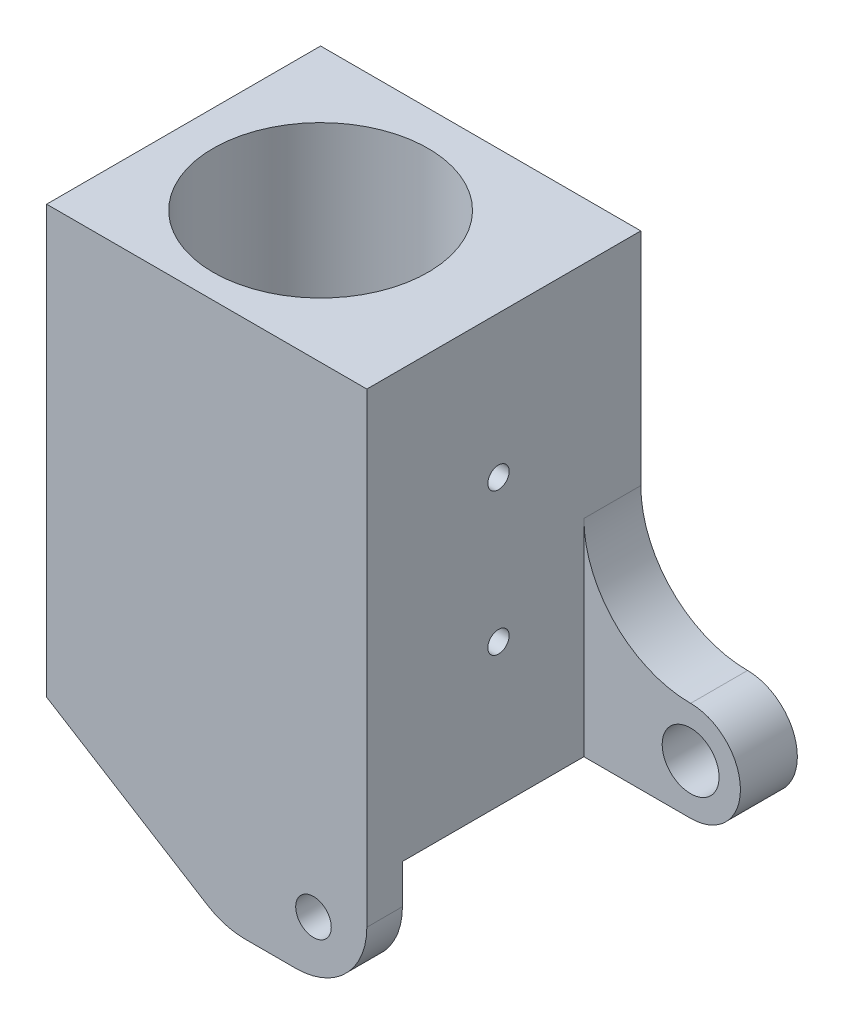
SolidWorks part; units mm, degrees
ref_plane "前基準面" through (0, 0, 0) normal (0, 0, 1) x (1, 0, 0)
ref_plane "上基準面" through (0, 0, 0) normal (0, 1, 0) x (1, 0, 0)
ref_plane "右基準面" through (0, 0, 0) normal (1, 0, 0) x (0, 0, -1)
sketch "草圖1" plane through (0, 0, 0) normal (0, 1, 0) x (1, 0, 0)
  line L1 (-20, 20) -> (25, 20)
  line L2 (-20, 20) -> (-20, -18.5)
  line L3 (-20, -18.5) -> (25, -18.5)
  line L4 (25, 20) -> (25, -18.5)
  dimension "D1" = 20
  dimension "D2" = 38.5
  dimension "D3" = 45
  dimension "D4" = 20
extrude "填料-伸長1" add sketch "草圖1" along normal blind 60
sketch "草圖2" plane through (0, 60, 0) normal (0, 1, 0) x (1, 0, 0)
  circle A0 centre (0, 0) radius 15.1
  dimension "D1" = 30.2
extrude "除料-伸長1" cut sketch "草圖2" against normal blind 50
sketch "草圖3" plane through (0, 0, 18.5) normal (0, 0, 1) x (1, 0, 0)
  line L1 (-20, 0) -> (5, -15.5)
  line L2 (5, -15.5) -> (25, -15.5)
  line L3 (25, -15.5) -> (25, 0)
  line L4 (25, 0) -> (-20, 0)
  circle A1 centre (17.5, -8) radius 2.5
  dimension "D1" = 5
  dimension "D2" = 20
  dimension "D3" = 15.5
  dimension "D4" = 7.5
  dimension "D5" = 8
extrude "填料-伸長2" add sketch "草圖3" against normal blind 5
sketch "草圖4" plane through (25, 0, 0) normal (1, 0, 0) x (0, 0, -1)
  circle A0 centre (0, 20) radius 1.5
  dimension "D1" = 3
  dimension "D2" = 20
extrude "除料-伸長2" cut sketch "草圖4" against normal through all
pattern_linear "直線複製排列1" count 2 spacing 20 along (0, 1, 0) of "除料-伸長2"
fillet "圓角1" radius 10 2 edges at (25, -15.5, 16) (5, -15.5, 16)
sketch "草圖5" plane through (0, 0, -20) normal (0, 0, -1) x (-1, 0, 0)
  line L1 (-25, 0) -> (-40, 0)
  line L2 (-25, 0) -> (-25, 14)
  line L3 (-25, 14) -> (-40, 14)
  arc A0 (-40, 14) -> (-40, 0) centre (-40, 7) ccw
  circle A1 centre (-40, 7) radius 4
  dimension "D2" = 14
  dimension "D3" = 8
  dimension "D1" = 15
extrude "填料-伸長3" add sketch "草圖5" against normal blind 8
fillet "圓角2" radius 15 1 edges at (25, 14, -16)
